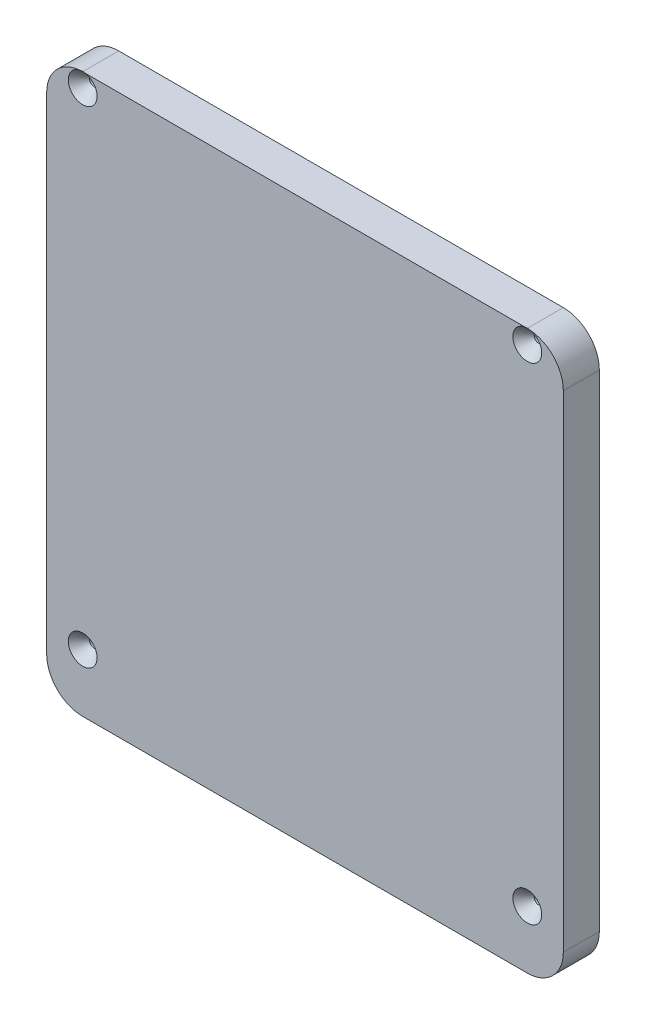
SolidWorks part; units mm, degrees
material "Beech"
ref_plane "Front Plane" through (0, 0, 0) normal (0, 0, 1) x (1, 0, 0)
ref_plane "Top Plane" through (0, 0, 0) normal (0, 1, 0) x (1, 0, 0)
ref_plane "Right Plane" through (0, 0, 0) normal (1, 0, 0) x (0, 0, -1)
sketch "Sketch1" plane through (0, 0, 0) normal (0, 0, 1) x (1, 0, 0)
  line L0 (139.05, 899.8522) -> (139.05, 151.949) construction
  line L1 (-43.1, 899.8522) -> (-43.1, 151.949) construction
  line L2 (-43.1, 906.2022) -> (139.05, 906.2022) construction
  line L8 (139.05, 668.0772) -> (139.05, 864.9272)
  line L9 (139.05, 864.9272) -> (-43.1, 864.9272)
  line L10 (-43.1, 864.9272) -> (-43.1, 668.0772)
  line L11 (-43.1, 668.0772) -> (139.05, 668.0772)
  dimension "D1" = 196.85
  dimension "D2" = 41.275
extrude "Boss-Extrude1" add sketch "Sketch1" along normal blind 12.7
fillet "Fillet1" radius 12.7 4 edges at (139.05, 864.9272, 6.35) (139.05, 668.0772, 6.35) (-43.1, 668.0772, 6.35) (-43.1, 864.9272, 6.35)
hole_wizard "Hole1" positions "Sketch2" profile "Sketch3" legacy
sketch "Sketch2" plane through (47.975, -433.1153, 12.7) normal (0, 0, 1) x (1, 0, 0)
  point P0 (-78.375, 1293.0392)
  point P3 (-78.375, 1121.5892)
  point P6 (78.375, 1121.5892)
  point P9 (78.375, 1293.0392)
  point P12 (-764.0155, 1530.0782)
sketch "Sketch3" plane through (-30.4, 859.9239, 12.7) normal (1, 0, 0) x (0, -1, 0)
  line L0 (0, 0) -> (0, 32.7039)
  line L1 (0, 32.7039) -> (1.5875, 31.75)
  line L2 (1.5875, 31.75) -> (1.5875, 4.0177)
  line L3 (1.5875, 4.0177) -> (5.08, 0)
  line L4 (5.08, 0) -> (0, 0)
  line L5 (0, -14.3089) -> (0, 102.4216) construction
  line L6 (0, 32.7039) -> (-1.5875, 31.75) construction
  line L7 (-1.5875, 4.0177) -> (-5.08, 0) construction
  dimension "Diameter" = 3.175
  dimension "Depth" = 31.75
  dimension "C-Sink Diameter" = 10.16
  dimension "C-Sink Angle" = 82
  dimension "Drill Angle" = 118
